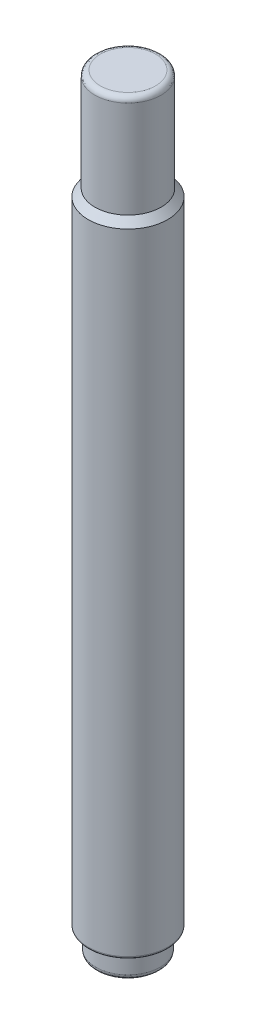
SolidWorks part; units mm, degrees
ref_plane "Front Plane" through (0, 0, 0) normal (0, 0, 1) x (1, 0, 0)
ref_plane "Top Plane" through (0, 0, 0) normal (0, 1, 0) x (1, 0, 0)
ref_plane "Right Plane" through (0, 0, 0) normal (1, 0, 0) x (0, 0, -1)
ref_axis "Axis1" through (-33.0333, 0, 0) along (1, 0, 0)
ref_axis "Axis2" through (0, 24.5224, 0) along (0, -1, 0)
ref_axis "Axis3" through (0, 0, -52.9538) along (0, 0, 1)
sketch "Sketch2" plane through (0, 0, 0) normal (0, 0, 1) x (1, 0, 0)
  line L0 (0, 72.25) -> (0, -72.25)
  line L1 (0, -72.25) -> (5.85, -72.25)
  line L2 (5.85, -72.25) -> (5.85, -67.75)
  line L3 (5.85, -67.75) -> (7.2, -67.75)
  line L4 (7.2, -67.75) -> (7.2, 51.55)
  line L5 (7.2, 51.55) -> (6, 52.95)
  line L6 (6, 52.95) -> (6, 72.25)
  line L7 (6, 72.25) -> (0, 72.25)
  point P2 (0, 0)
  dimension "D1" = 144.5
  dimension "D2" = 5.85
  dimension "D3" = 7.2
  dimension "D4" = 19.3
  dimension "D5" = 4.5
  dimension "D6" = 6
  dimension "D7" = 20.7
revolve "Revolve1" add sketch "Sketch2" angle 360 about L0
fillet "Fillet1" radius 0.475 2 edges at (-5.85, -67.75, 0) (-7.2, -67.75, 0)
fillet "Fillet4" radius 1 2 edges at (-5.85, -72.25, 0) (-6, 72.25, 0)
scale "Scale1" scale about origin uniform scaling no x scale factor 1.05 y scale factor 1.01 z scale factor 1.05
